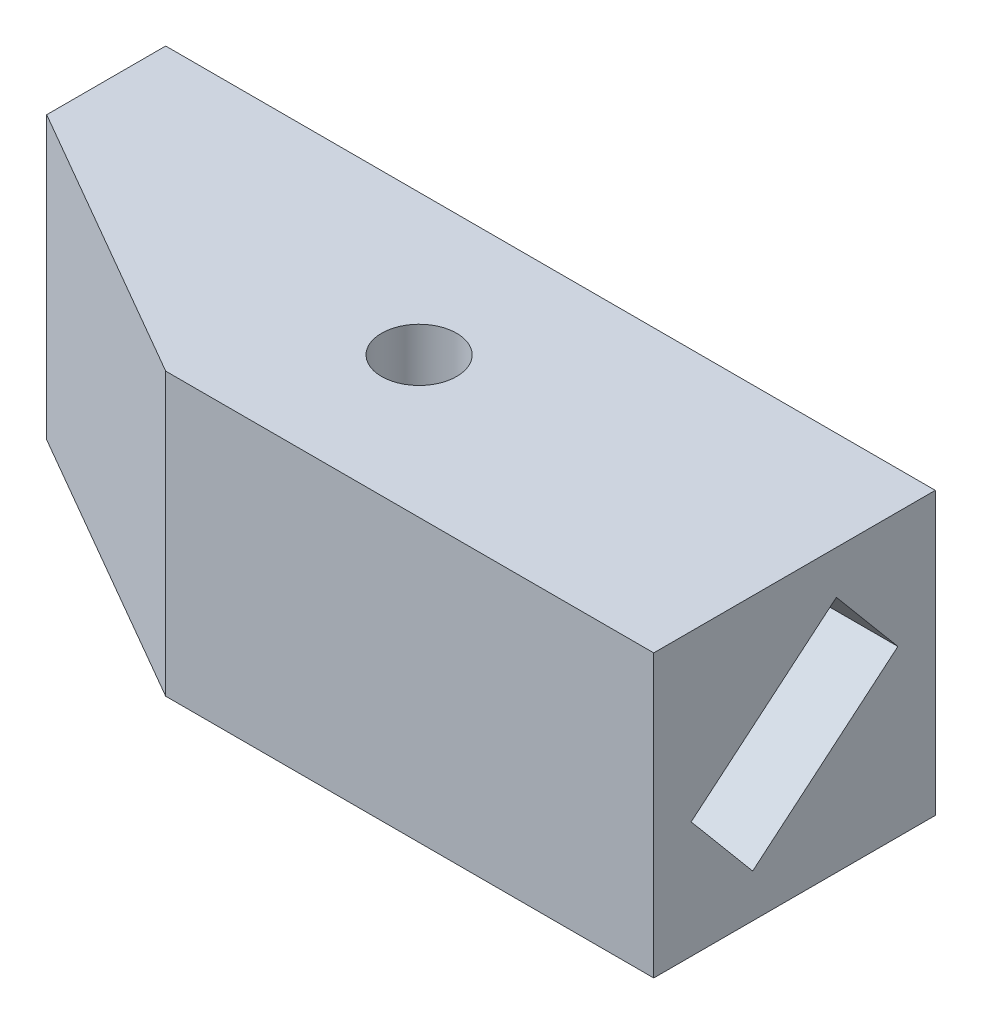
SolidWorks part; units mm, degrees
ref_plane "Спереди" through (0, 0, 0) normal (0, 0, 1) x (1, 0, 0)
ref_plane "Сверху" through (0, 0, 0) normal (0, 1, 0) x (1, 0, 0)
ref_plane "Справа" through (0, 0, 0) normal (1, 0, 0) x (0, 0, -1)
sketch "Эскиз1" plane through (0, 0, 0) normal (0, 1, 0) x (1, 0, 0)
  line L0 (-20, 15) -> (-35, 15)
  line L1 (-20, -15) -> (20, -15)
  line L2 (-35, 15) -> (-35, -15)
  line L3 (-20, 15) -> (20, 15)
  line L4 (20, -15) -> (20, 15)
  line L5 (-20, -15) -> (20, 15) construction
  line L6 (-20, 15) -> (20, -15) construction
  line L7 (-35, -15) -> (-20, -15)
  point P0 (0, 0)
  dimension "D1" = 40
  dimension "D2" = 30
  dimension "D3" = 15
extrude "Бобышка-Вытянуть1" add sketch "Эскиз1" along normal blind 30
sketch "Эскиз2" plane through (0, 30, 0) normal (0, 1, 0) x (1, 0, 0)
  line L0 (-20, -15) -> (-20, 15) construction
  circle A0 centre (-20, 0) radius 4
  dimension "D1" = 15
extrude "Вырез-Вытянуть1" cut sketch "Эскиз2" against normal through all
sketch "Эскиз5" plane through (20, 0, 0) normal (1, 0, 0) x (0, 0, -1)
  line L0 (0, 30) -> (0, 0) construction
  line L1 (-15, 30) -> (15, 0) construction
  line L2 (-15, 0) -> (15, 0) construction
  line L4 (11.0153, 17.5853) -> (4.4588, 25.399)
  line L5 (11.0153, 17.5853) -> (-4.4588, 4.601)
  line L6 (-4.4588, 4.601) -> (-11.0153, 12.4147)
  line L7 (4.4588, 25.399) -> (-11.0153, 12.4147)
  line L8 (11.0153, 17.5853) -> (-11.0153, 12.4147) construction
  line L9 (-4.4588, 4.601) -> (4.4588, 25.399) construction
  point P5 (0, 15)
  point P6 (0, 15)
  dimension "D1" = 20.2
  dimension "D2" = 10.2
  dimension "D3" = 40
extrude "Вырез-Вытянуть4" cut sketch "Эскиз5" against normal blind 30
sketch "Sketch1" plane through (-35, 0, 0) normal (-1, 0, 0) x (0, 0, 1)
  line L0 (0, 30) -> (0, 0) construction
  line L1 (-15, 30) -> (15, 30) construction
  line L2 (-15, 0) -> (15, 0) construction
  line L4 (-15, 0) -> (15, 0)
  line L5 (-15, 0) -> (-15, 30)
  line L6 (-15, 30) -> (15, 30)
  line L7 (15, 0) -> (15, 30)
  line L8 (-15, 0) -> (15, 30) construction
  line L9 (-15, 30) -> (15, 0) construction
  point P6 (0, 15)
extrude "Boss-Extrude1" add sketch "Sketch1" along normal blind 27
chamfer "Chamfer1" distance 30 angle 30 1 edges at (-62, 15, 15) first distance on face at (-21, 15, 15)
